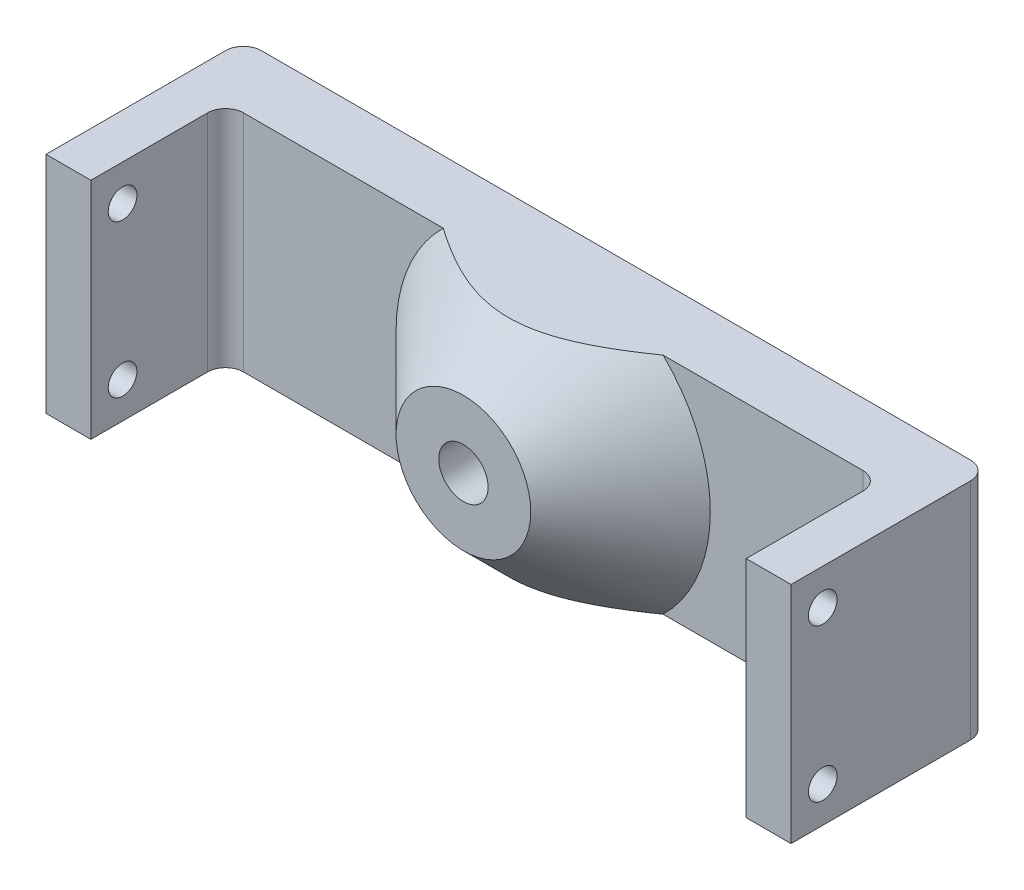
SolidWorks part; units mm, degrees
ref_plane "Płaszczyzna przednia" through (0, 0, 0) normal (0, 0, 1) x (1, 0, 0)
ref_plane "Płaszczyzna górna" through (0, 0, 0) normal (0, 1, 0) x (1, 0, 0)
ref_plane "Płaszczyzna prawa" through (0, 0, 0) normal (1, 0, 0) x (0, 0, -1)
sketch "Szkic1" plane through (0, 0, 0) normal (0, 0, 1) x (1, 0, 0)
  line L1 (41.5, 12.5) -> (-41.5, 12.5)
  line L2 (41.5, 12.5) -> (41.5, -12.5)
  line L3 (41.5, -12.5) -> (-41.5, -12.5)
  line L4 (-41.5, 12.5) -> (-41.5, -12.5)
  line L5 (41.5, 12.5) -> (-41.5, -12.5) construction
  line L6 (41.5, -12.5) -> (-41.5, 12.5) construction
  point P0 (0, 0)
  dimension "D1" = 83
  dimension "D2" = 25
extrude "Dodanie-wyciągnięcie1" add sketch "Szkic1" along normal blind 7
sketch "Szkic2" plane through (0, 0, 7) normal (0, 0, 1) x (1, 0, 0)
  line L0 (-41.5, -12.5) -> (41.5, -12.5) construction
  line L1 (-41.5, 12.5) -> (-36.5, 12.5)
  line L2 (-41.5, 12.5) -> (-41.5, -12.5)
  line L3 (-41.5, -12.5) -> (-36.5, -12.5)
  line L4 (-36.5, 12.5) -> (-36.5, -12.5)
  line L6 (41.5, 12.5) -> (36.5, 12.5)
  line L7 (41.5, 12.5) -> (41.5, -12.5)
  line L8 (41.5, -12.5) -> (36.5, -12.5)
  line L9 (36.5, 12.5) -> (36.5, -12.5)
  dimension "D1" = 5
  dimension "D2" = 5
extrude "Dodanie-wyciągnięcie2" add sketch "Szkic2" along normal blind 15
sketch "Szkic3" plane through (41.5, 0, 0) normal (1, 0, 0) x (0, 0, -1)
  line L0 (-18.47, 12.5) -> (-18.47, -12.5) construction
  line L1 (-22, 12.5) -> (0, 12.5) construction
  line L2 (-22, -12.5) -> (0, -12.5) construction
  line L3 (-22, 0) -> (0, 0) construction
  line L4 (-22, -12.5) -> (-22, 12.5) construction
  circle A0 centre (-18.47, 8.5) radius 1.6
  circle A1 centre (-18.47, -8.5) radius 1.6
  dimension "D3" = 3.2
  dimension "D4" = 3.2
  dimension "D1" = 8.5
  dimension "D2" = 8.5
extrude "Wytnij-wyciągnięcie1" cut sketch "Szkic3" against normal up to surface (83 mm away) up to face at (-41.5, 0, 11)
sketch "Szkic4" plane through (0, 0, 7) normal (0, 0, 1) x (1, 0, 0)
  circle A0 centre (0, 0) radius 7.5
  dimension "D1" = 15
extrude "Dodanie-wyciągnięcie4" add sketch "Szkic4" along normal blind 10
sketch "Szkic5" plane through (0, 0, 17) normal (0, 0, 1) x (1, 0, 0)
  circle A0 centre (0, 0) radius 2.75
  dimension "D1" = 5.5
extrude "Wytnij-wyciągnięcie2" cut sketch "Szkic5" against normal up to surface (17 mm away) up to face at (0, 0, 0)
chamfer "Sfazowanie1" distance 10 angle 45 1 edges at (-7.5, 0, 7)
fillet "Zaokrąglenie1" radius 2 2 edges at (-36.5, 0, 7) (36.5, 0, 7)
fillet "Zaokrąglenie2" radius 2 2 edges at (-41.5, 0, 0) (41.5, 0, 0)
